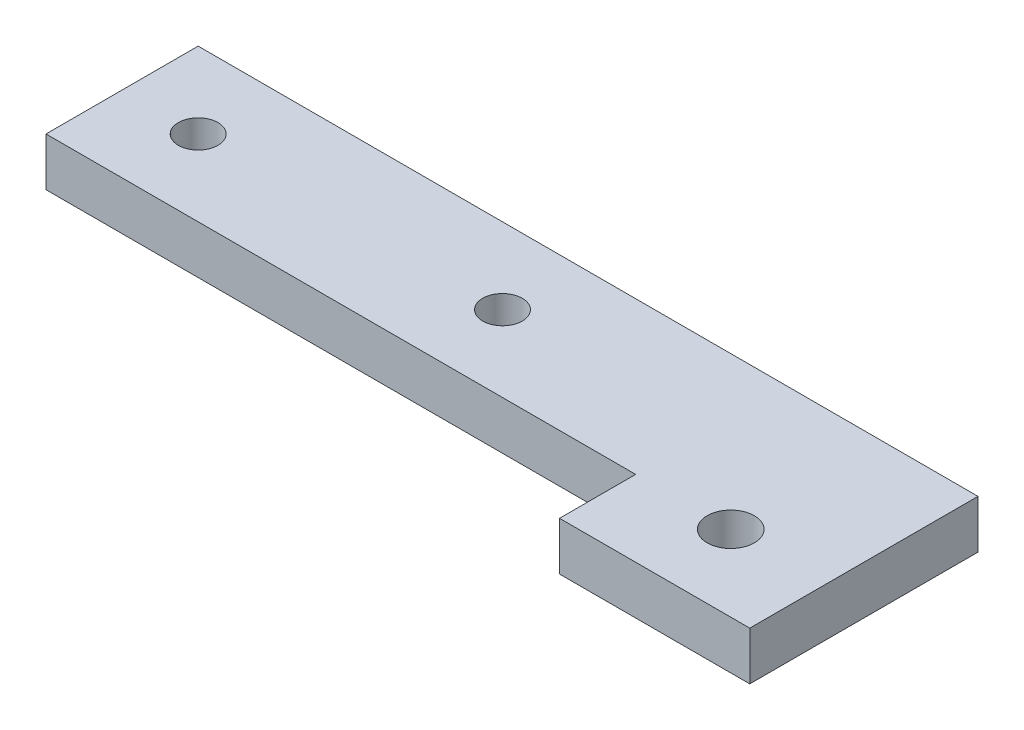
SolidWorks part; units mm, degrees
material "1060 Alloy"
ref_plane "Front Plane" through (0, 0, 0) normal (0, 0, 1) x (1, 0, 0)
ref_plane "Top Plane" through (0, 0, 0) normal (0, 1, 0) x (1, 0, 0)
ref_plane "Right Plane" through (0, 0, 0) normal (1, 0, 0) x (0, 0, -1)
sketch "Sketch1" plane through (0, 0, 0) normal (0, 1, 0) x (1, 0, 0)
  line L1 (-12.5, 0) -> (12.5, 0) construction
  line L2 (-12.5, 0) -> (-12.5, -10)
  line L3 (-12.5, -10) -> (12.5, -10)
  line L4 (12.5, 0) -> (12.5, -10)
  line L5 (-12.5, 0) -> (12.5, -10) construction
  line L6 (-12.5, -10) -> (12.5, 0) construction
  line L11 (0, 3.1) -> (0, 0) construction
  line L12 (0, 0) -> (0, -5) construction
  line L20 (12.5, 20) -> (-90, 20)
  line L21 (-90, 20) -> (-90, 0)
  line L24 (12.5, 0) -> (12.5, 20)
  line L25 (-40, 10) -> (-80, 10) construction
  line L26 (-12.5, 0) -> (-90, 0)
  line L27 (0, 0) -> (0, 20) construction
  line L28 (-30, 0) -> (-30, 20) construction
  circle A0 centre (0, 0) radius 3.1
  circle A3 centre (-40, 10) radius 2.6
  circle A4 centre (-80, 10) radius 2.6
  point P16 (0, -5)
  point P20 (-60, 10)
  dimension "D1" = 6.2
  dimension "D5" = 5.2
  dimension "D7" = 5.2
  dimension "D2" = 25
  dimension "D3" = 10
  dimension "D4" = 10
  dimension "D6" = 5
  dimension "D8" = 10
  dimension "D9" = 10
  dimension "D10" = 30
  dimension "D11" = 40
  dimension "D12" = 10
extrude "Boss-Extrude1" add sketch "Sketch1" along normal blind 3.175 and the other way blind 3.175
